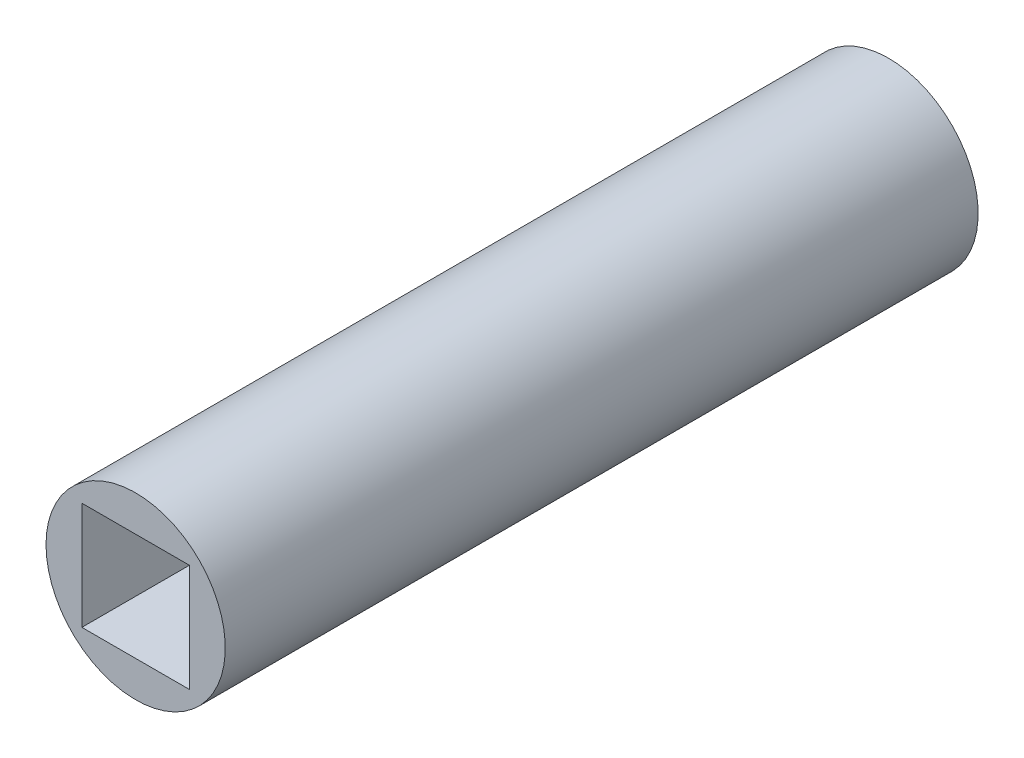
SolidWorks part; units mm, degrees
material "PLA"
ref_plane "Front Plane" through (0, 0, 0) normal (0, 0, 1) x (1, 0, 0)
ref_plane "Top Plane" through (0, 0, 0) normal (0, 1, 0) x (1, 0, 0)
ref_plane "Right Plane" through (0, 0, 0) normal (1, 0, 0) x (0, 0, -1)
sketch "Sketch1" plane through (0, 0, 0) normal (0, 1, 0) x (1, 0, 0)
  line L1 (0, 0) -> (-15.875, 0)
  line L2 (0, 0) -> (0, -133.35)
  line L3 (0, -133.35) -> (-15.875, -133.35)
  line L4 (-15.875, 0) -> (-15.875, -133.35)
  dimension "D1" = 133.35
  dimension "D2" = 15.875
revolve "Revolve1" add sketch "Sketch1" angle 360 about L2
sketch "Sketch2" plane through (0, 0, 133.35) normal (0, 0, 1) x (1, 0, 0)
  line L1 (-9.525, 9.525) -> (9.525, 9.525)
  line L2 (-9.525, 9.525) -> (-9.525, -9.525)
  line L3 (-9.525, -9.525) -> (9.525, -9.525)
  line L4 (9.525, 9.525) -> (9.525, -9.525)
  line L5 (-9.525, 9.525) -> (9.525, -9.525) construction
  line L6 (-9.525, -9.525) -> (9.525, 9.525) construction
  point P0 (0, 0)
  dimension "D1" = 19.05
  dimension "D2" = 19.05
extrude "Cut-Extrude1" cut sketch "Sketch2" against normal through all contours L2 L1 L4 L3
